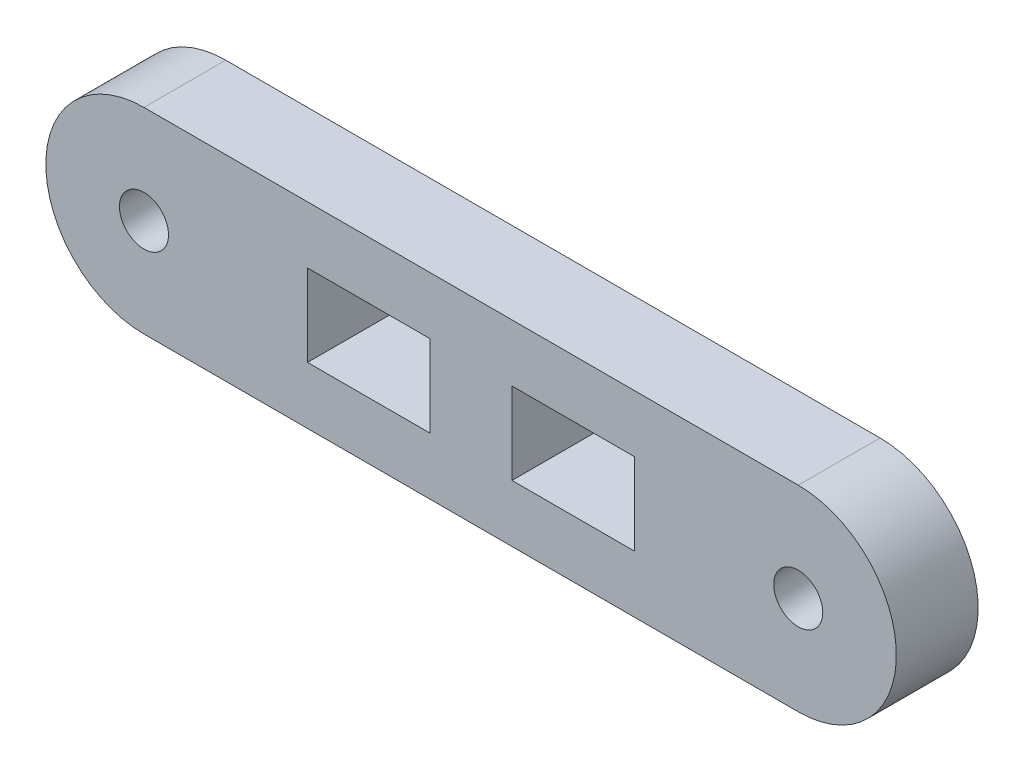
SolidWorks part; units mm, degrees
ref_plane "Plan de face" through (0, 0, 0) normal (0, 0, 1) x (1, 0, 0)
ref_plane "Plan de dessus" through (0, 0, 0) normal (0, 1, 0) x (1, 0, 0)
ref_plane "Plan de droite" through (0, 0, 0) normal (1, 0, 0) x (0, 0, -1)
sketch "Esquisse1" plane through (0, 0, 0) normal (0, 0, 1) x (1, 0, 0)
  line L0 (20, 6) -> (20, -6) construction
  line L2 (0, 0) -> (40, 0) construction
  line L4 (30, -2.5) -> (22.5, -2.5)
  line L5 (22.5, -2.5) -> (22.5, 2.5)
  line L6 (22.5, 2.5) -> (30, 2.5)
  line L7 (30, 2.5) -> (30, -2.5)
  line L8 (10, 2.5) -> (10, -2.5)
  line L9 (17.5, 2.5) -> (10, 2.5)
  line L10 (17.5, -2.5) -> (17.5, 2.5)
  line L11 (10, -2.5) -> (17.5, -2.5)
  line L12 (0, 0) -> (40, 0) construction
  line L13 (0, 6) -> (40, 6)
  line L14 (0, -6) -> (40, -6)
  arc A0 (0, 6) -> (0, -6) centre (0, 0) ccw
  arc A1 (40, -6) -> (40, 6) centre (40, 0) ccw
  circle A5 centre (40, 0) radius 1.5
  circle A6 centre (0, 0) radius 1.5
  point P0 (20, 0)
  dimension "D1" = 6
  dimension "D2" = 3
  dimension "D3" = 5
  dimension "D4" = 40
  dimension "D6" = 7.5
  dimension "D7" = 5
extrude "Boss.-Extru.1" add sketch "Esquisse1" along normal blind 5
